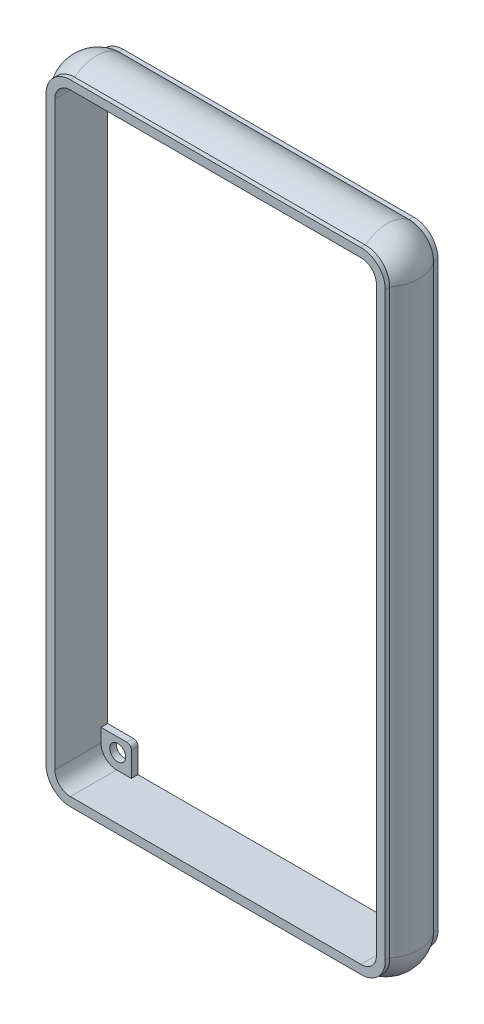
SolidWorks part; units mm, degrees
material "Plastique personnalisé"
ref_plane "Plan de face" through (0, 0, 0) normal (0, 0, 1) x (1, 0, 0)
ref_plane "Plan de dessus" through (0, 0, 0) normal (0, 1, 0) x (1, 0, 0)
ref_plane "Plan de droite" through (0, 0, 0) normal (1, 0, 0) x (0, 0, -1)
sketch "Model" plane through (0, 0, 0) normal (0, 0, 1) x (1, 0, 0)
  line L0 (62.865, -88.2411) -> (128.905, -88.2411)
  line L3 (59.331, -91.7751) -> (59.331, -223.8578) construction
  line L5 (62.865, -227.3917) -> (128.8982, -227.3917) construction
  line L45 (132.4454, -223.8438) -> (132.4454, -91.7796) construction
  line L51 (59.331, -91.7751) -> (59.331, -223.8578)
  line L52 (62.865, -227.3917) -> (128.8982, -227.3917)
  line L53 (132.4454, -223.8438) -> (132.4454, -91.7796)
  arc A0 (128.905, -88.2411) -> (132.4454, -91.7796) centre (128.9896, -91.6969) cw
  arc A1 (59.331, -91.7751) -> (62.865, -88.2411) centre (62.865, -91.7751) cw
  arc A2 (59.331, -223.8578) -> (62.865, -227.3917) centre (62.865, -223.8578) ccw
  arc A3 (128.8982, -227.3917) -> (132.4454, -223.8438) centre (129.0305, -223.9768) ccw
extrude "Boss.-Extru.1" add sketch "Model" along normal blind 10
shell "Coque3" thickness 2 removed face at (95.8945, -157.8173, 10) outward yes
sketch "Esquisse3" plane through (0, 0, 0) normal (0, 0, 1) x (1, 0, 0)
  line L0 (62.865, -88.2411) -> (128.905, -88.2411)
  line L3 (59.331, -91.7751) -> (59.331, -223.8578) construction
  line L5 (62.865, -227.3917) -> (128.8982, -227.3917) construction
  line L45 (132.4454, -223.8438) -> (132.4454, -91.7796) construction
  line L51 (59.331, -91.7751) -> (59.331, -223.8578)
  line L52 (62.865, -227.3917) -> (128.8982, -227.3917)
  line L53 (132.4454, -223.8438) -> (132.4454, -91.7796)
  arc A0 (128.905, -88.2411) -> (132.4454, -91.7796) centre (128.9896, -91.6969) cw
  arc A1 (59.331, -91.7751) -> (62.865, -88.2411) centre (62.865, -91.7751) cw
  arc A2 (59.331, -223.8578) -> (62.865, -227.3917) centre (62.865, -223.8578) ccw
  arc A3 (128.8982, -227.3917) -> (132.4454, -223.8438) centre (129.0305, -223.9768) ccw
extrude "Enlèv. mat.-Extru.4" cut sketch "Esquisse3" against normal blind 10
ref_plane "Plan1" through (66.8295, -96.3427, -2) normal (0.0013, -1, 0) x (-1, -0.0013, 0)
sketch "Esquisse5" plane through (0, 0, -2) normal (0, 0, -1) x (-1, 0, 0)
  line L0 (-125.9678, -88.7364) -> (-125.9678, -87.927)
  line L2 (-132.914, -88.7364) -> (-132.914, -95.2236)
  line L3 (-132.914, -95.2236) -> (-126.9678, -95.2236)
  line L4 (-125.9678, -88.7364) -> (-125.9678, -94.2236)
  line L5 (-125.9678, -87.927) -> (-130.4895, -87.7229)
  line L6 (-130.4895, -87.7229) -> (-132.2463, -88.3317)
  line L7 (-132.2463, -88.3317) -> (-132.914, -88.7364)
  line L8 (-95.8741, -86.2411) -> (-95.8741, -63.0628) construction
  line L9 (-128.8833, -86.2411) -> (-62.865, -86.2411) construction
  line L10 (-65.7805, -88.7364) -> (-65.7805, -87.927)
  line L11 (-65.7805, -87.927) -> (-61.2588, -87.7229)
  line L12 (-61.2588, -87.7229) -> (-59.502, -88.3317)
  line L13 (-59.502, -88.3317) -> (-58.8343, -88.7364)
  line L14 (-58.8343, -88.7364) -> (-58.8343, -95.2236)
  line L15 (-58.8343, -95.2236) -> (-64.7805, -95.2236)
  line L16 (-65.7805, -88.7364) -> (-65.7805, -94.2236)
  arc A0 (-64.7805, -95.2236) -> (-65.7805, -94.2236) centre (-64.7805, -94.2236) cw
  arc A1 (-126.9678, -95.2236) -> (-125.9678, -94.2236) centre (-126.9678, -94.2236) ccw
  circle A2 centre (-62.9575, -92.5512) radius 1.8
  circle A3 centre (-129.134, -92.4654) radius 1.8
  point P20 (-65.7805, -95.2236)
  point P23 (-125.9678, -95.2236)
  dimension "D1" = 1
extrude "Boss.-Extru.2" add sketch "Esquisse5" against normal blind 1.5
sketch "Esquisse6" plane through (0, 0, -2) normal (0, 0, -1) x (-1, 0, 0)
  line L0 (-133.3394, -220.7658) -> (-126.5042, -220.7658)
  line L1 (-125.5042, -221.7658) -> (-125.5042, -228.0641)
  line L2 (-125.5042, -228.0641) -> (-130.168, -228.0641)
  line L3 (-130.168, -228.0641) -> (-131.7334, -227.2509)
  line L4 (-131.7334, -227.2509) -> (-133.3394, -225.1773)
  line L5 (-133.3394, -225.1773) -> (-133.3394, -220.7658)
  line L6 (-95.8644, -229.3917) -> (-95.8644, -240.0509) construction
  line L7 (-62.865, -229.3917) -> (-128.8639, -229.3917) construction
  line L8 (-58.3895, -225.1773) -> (-58.3895, -220.7658)
  line L9 (-59.9955, -227.2509) -> (-58.3895, -225.1773)
  line L10 (-61.5608, -228.0641) -> (-59.9955, -227.2509)
  line L11 (-66.2247, -228.0641) -> (-61.5608, -228.0641)
  line L12 (-66.2247, -221.7658) -> (-66.2247, -228.0641)
  line L13 (-58.3895, -220.7658) -> (-65.2247, -220.7658)
  arc A0 (-66.2247, -221.7658) -> (-65.2247, -220.7658) centre (-65.2247, -221.7658) cw
  arc A1 (-126.5042, -220.7658) -> (-125.5042, -221.7658) centre (-126.5042, -221.7658) cw
  circle A2 centre (-63.1208, -223.851) radius 1.8098
  circle A3 centre (-129.1608, -223.7655) radius 1.8
  point P18 (-66.2247, -220.7658)
  point P21 (-125.5042, -220.7658)
  dimension "D1" = 1
extrude "Boss.-Extru.3" add sketch "Esquisse6" against normal blind 1.5
ref_plane "Plan2" through (0, 0, 5) normal (0, 0, 1) x (1, 0, 0)
sketch "Esquisse7" plane through (0, 0, 5) normal (0, 0, 1) x (1, 0, 0)
  line L0 (128.8833, -86.2411) -> (128.8833, -84.7411) construction
  line L1 (128.8833, -84.7411) -> (50.3833, -84.7411) construction
  line L2 (57.331, -91.7751) -> (55.831, -91.7751) construction
  line L3 (58.9519, -87.862) -> (57.8912, -86.8013) construction
  line L4 (55.831, -91.7751) -> (55.831, -235.7649) construction
  line L5 (134.4464, -91.6969) -> (135.9427, -91.6969) construction
  line L6 (135.9427, -91.6969) -> (135.9427, -232.3576) construction
  line L7 (125.3053, -229.3917) -> (125.3053, -230.8876) construction
  line L8 (62.865, -229.3917) -> (128.8639, -229.3917) construction
  line L9 (125.3053, -230.8876) -> (137.6798, -230.8876) construction
  line L11 (128.9427, -230.8876) -> (62.831, -230.8876)
  line L12 (135.9427, -223.8876) -> (135.9427, -91.7411)
  line L13 (128.9427, -84.7411) -> (62.831, -84.7411)
  line L14 (55.831, -223.8876) -> (55.831, -91.7411)
  arc A0 (62.865, -86.2411) -> (57.331, -91.7751) centre (62.865, -91.7751) ccw construction
  arc A1 (134.4454, -91.8008) -> (128.8833, -86.2411) centre (128.9896, -91.6969) ccw construction
  arc A2 (62.831, -230.8876) -> (55.831, -223.8876) centre (62.831, -223.8876) cw
  arc A3 (128.9427, -230.8876) -> (135.9427, -223.8876) centre (128.9427, -223.8876) ccw
  arc A4 (135.9427, -91.7411) -> (128.9427, -84.7411) centre (128.9427, -91.7411) ccw
  arc A5 (62.831, -84.7411) -> (55.831, -91.7411) centre (62.831, -91.7411) ccw
  point P33 (135.9427, -230.8876)
  point P38 (55.831, -84.7411)
  dimension "D4" = 7
  dimension "D1" = 1.5
  dimension "D2" = 1.5
  dimension "D3" = 1.5
ref_plane "Plan3" through (0, -155, 0) normal (0, 1, 0) x (1, 0, 0)
sketch "Esquisse8" plane through (0, -155, 0) normal (0, 1, 0) x (1, 0, 0)
  line L0 (57.331, 2) -> (57.331, 1.0015) construction
  line L1 (57.331, -10) -> (57.331, 2) construction
  line L2 (57.331, -10) -> (57.331, -9.0032) construction
  line L3 (57.331, 1.0015) -> (57.331, -9.0032)
  arc A0 (57.331, 1.0015) -> (57.331, -9.0032) centre (63.5966, -4.0009) ccw
sweep "Balayage1" add profiles "Esquisse8" path "Esquisse7"
